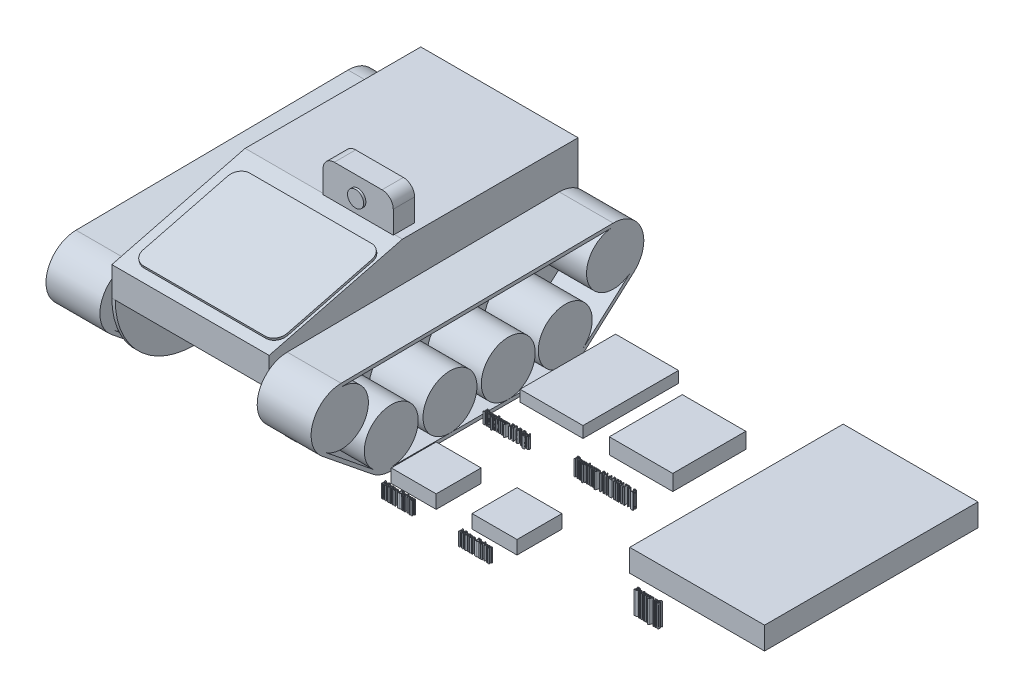
SolidWorks part; units mm, degrees
ref_plane "Спереди" through (0, 0, 0) normal (0, 0, 1) x (1, 0, 0)
ref_plane "Сверху" through (0, 0, 0) normal (0, 1, 0) x (1, 0, 0)
ref_plane "Справа" through (0, 0, 0) normal (1, 0, 0) x (0, 0, -1)
sketch "Эскиз1" plane through (0, 0, 0) normal (1, 0, 0) x (0, 0, -1)
  line L2 (-118.6213, 23.4128) -> (-118.6213, -46.5872)
  line L3 (-118.6213, -46.5872) -> (156.3787, -46.5872)
  line L4 (156.3787, 23.4128) -> (156.3787, -46.5872)
  line L14 (-118.6213, 23.4128) -> (156.3787, 23.4128)
  dimension "D1" = 275
  dimension "D2" = 70
extrude "Бобышка-Вытянуть5" add sketch "Эскиз1" against normal blind 3 contours L14 L2 L3 L4
sketch "Эскиз3" plane through (0, 0, 0) normal (1, 0, 0) x (0, 0, -1)
  line L0 (-118.6213, 49.2471) -> (0, 79.5354)
  line L1 (-118.6213, 23.4128) -> (156.3787, 23.4128)
  line L2 (-118.6213, 23.4128) -> (-118.6213, 49.2471)
  line L3 (-118.6213, 49.2471) -> (156.3787, 49.2471)
  line L4 (156.3787, 23.4128) -> (156.3787, 49.2471)
  line L5 (0, 79.5354) -> (156.3787, 79.5354)
  line L6 (156.3787, 79.5354) -> (156.3787, 49.2471)
  dimension "D1" = 275
extrude "Бобышка-Вытянуть6" add sketch "Эскиз3" against normal blind 70 contours L1 L4 L3 L2 | L6 L5 L0 L3
sketch "Эскиз4" plane through (0, 0, 0) normal (1, 0, 0) x (0, 0, -1)
  line L0 (-102.494, 40.7208) -> (139.6566, 43.1324)
  line L1 (-117.341, -1.9438) -> (-73.0232, -37.7622)
  line L2 (155.8507, 1.205) -> (112.8921, -37.025)
  line L3 (-57.9372, -43.0964) -> (96.937, -43.0964)
  line L4 (-102.5239, 43.7206) -> (139.6267, 46.1323)
  line L5 (157.8451, -1.036) -> (114.8865, -39.266)
  line L6 (-57.9372, -46.0964) -> (96.937, -46.0964)
  line L7 (-119.2268, -4.2771) -> (-74.9089, -40.0954)
  arc A0 (-102.494, 40.7208) -> (-117.341, -1.9438) centre (-102.255, 16.722) ccw
  arc A2 (-73.0232, -37.7622) -> (-57.9372, -43.0964) centre (-57.9372, -19.0964) ccw
  arc A11 (96.937, -43.0964) -> (112.8921, -37.025) centre (96.937, -19.0964) ccw
  arc A12 (155.8507, 1.205) -> (139.6566, 43.1324) centre (139.8956, 19.1336) ccw
  circle A13 centre (-102.255, 16.722) radius 24
  circle A16 centre (96.937, -19.0964) radius 24
  circle A19 centre (139.8956, 19.1336) radius 24
  circle A20 centre (-57.9372, -19.0964) radius 24
  circle A21 centre (-5.6546, -19.0964) radius 24
  circle A22 centre (46.2242, -19.0964) radius 24
  arc A23 (157.8451, -1.036) -> (139.6267, 46.1323) centre (139.8956, 19.1336) ccw
  arc A24 (96.937, -46.0964) -> (114.8865, -39.266) centre (96.937, -19.0964) ccw
  arc A25 (-74.9089, -40.0954) -> (-57.9372, -46.0964) centre (-57.9372, -19.0964) ccw
  arc A26 (-102.5239, 43.7206) -> (-119.2268, -4.2771) centre (-102.255, 16.722) ccw
  line M1 (156.3787, -46.5872) -> (156.3787, 79.5354)
  line M4 (-118.6213, 49.2471) -> (-118.6213, -46.5872)
  dimension "D1" = 3
extrude "Бобышка-Вытянуть7" add sketch "Эскиз4" along normal blind 48 separate body contours A2 A20 | A0 A13 M4 | A0 M4 | A21 | A22 | A11 A16 | A22 A19 M1 | A22 M1 | L7 A25 L6 A24 L5 A22 L2 A11 L3 A2 L1 A0 M1 M4 | L5 A23 A22 M1 | L4 A26 A0 L0 A22 A23 M4 M1 | A26 L7 A0 M4
ref_plane "Плоскость5" through (-70, 0, 0) normal (-1, 0, 0) x (0, 0, 1)
mirror "Зеркальное отражение1" about plane through (-70, 0, 0) normal (-1, 0, 0) of bodies 108 111 112 107
fillet "Скругление1" radius 70 2 edges at (-3, -11.5872, 118.6213) (-1.5, -46.5872, 118.6213)
fillet "Скругление2" radius 70 2 edges at (-3, -11.5872, -156.3787) (-1.5, -46.5872, -156.3787)
fillet "Скругление3" radius 70 2 edges at (-137, -11.5872, -156.3787) (-138.5, -46.5872, -156.3787)
fillet "Скругление4" radius 70 2 edges at (-137, -11.5872, 118.6213) (-138.5, -46.5872, 118.6213)
ref_plane "Плоскость6" through (0, 0, 0) normal (0, 0, -1) x (1, 0, 0)
sketch "Эскиз10" plane through (0, 0, 0) normal (0, 0, -1) x (1, 0, 0)
  line L0 (-70, -79.5354) -> (0, -79.5354) construction
  line L1 (-69.6217, -109.5354) -> (-7.1459, -109.5354)
  line L2 (-69.6217, -109.5354) -> (-69.6217, -79.5354)
  line L3 (-69.6217, -79.5354) -> (-7.1459, -79.5354)
  line L4 (-7.1459, -109.5354) -> (-7.1459, -79.5354)
  dimension "D1" = 30
extrude "Бобышка-Вытянуть14" add sketch "Эскиз10" against normal blind 1 and the other way blind 18
sketch "Эскиз12" plane through (0, -8.4881, 1) normal (0, 0, 1) x (1, 0, 0)
  circle A0 centre (-38.6725, 101.334) radius 7.1777
extrude "Бобышка-Вытянуть15" add sketch "Эскиз12" along normal blind 2
fillet "Скругление5" radius 10 1 edges at (-7.1459, 109.5354, -8.5)
fillet "Скругление6" radius 10 1 edges at (-69.6217, 109.5354, -8.5)
ref_plane "Плоскость7" through (0, 74.6673, 19.0653) normal (0, -0.9689, -0.2474) x (-1, 0, 0)
sketch "Эскиз13" plane through (0, 74.6673, 19.0653) normal (0, 0.9689, 0.2474) x (1, 0, 0)
  line L0 (-130.6595, 4.4916) -> (-130.6595, -93.1708)
  line L1 (-127.6595, 1.4916) -> (-5.27, 1.4916)
  line L2 (-127.6595, 1.4916) -> (-127.6595, -90.1708)
  line L3 (-127.6595, -90.1708) -> (-5.27, -90.1708)
  line L4 (-5.27, 1.4916) -> (-5.27, -90.1708)
  line L9 (-130.6595, -93.1708) -> (-2.27, -93.1708)
  line L10 (-2.27, 4.4916) -> (-2.27, -93.1708)
  line L11 (-130.6595, 4.4916) -> (-2.27, 4.4916)
  line M11 (-70, -102.7501) -> (-70, 19.6769)
  dimension "D1" = 3
extrude "Бобышка-Вытянуть16" add sketch "Эскиз13" along direction (0, -0.9689, -0.2474) on the side of the normal blind 2 contours L4 L1 L3 M11 | L2 L3 L1 M11 | L11 L0 L9 L3 L2 L1 M11 | L11 L1 L4 L3 L9 L10 M11
fillet "Скругление7" radius 10 1 edges at (-2.27, 76.7475, 14.9607)
fillet "Скругление8" radius 10 1 edges at (-2.27, 52.5859, 109.5871)
fillet "Скругление9" radius 10 1 edges at (-130.6595, 52.5859, 109.5871)
fillet "Скругление10" radius 10 1 edges at (-130.6595, 76.7475, 14.9607)
sketch "Эскиз16" plane through (0, 0, 0) normal (0, 0, -1) x (1, 0, 0)
  circle A0 centre (-38.6725, -92.8459) radius 2
  circle A2 centre (-38.6725, -92.8459) radius 4
extrude "Вырез-Вытянуть1" cut sketch "Эскиз16" against normal blind 1
sketch "Эскиз18" plane through (0, 0, 45.2657) normal (0, 1, 0) x (1, 0, 0)
  line L1 (98.5208, 136.4886) -> (154.5208, 136.4886)
  line L2 (98.5208, 136.4886) -> (98.5208, 51.4886)
  line L3 (98.5208, 51.4886) -> (154.5208, 51.4886)
  line L4 (154.5208, 136.4886) -> (154.5208, 51.4886)
  text T0 "Raspberry PI 5 8gb"
  dimension "D1" = 85
  dimension "D2" = 56
extrude "Raspberry_PI5" add sketch "Эскиз18" along normal blind 10 separate body
sketch "Эскиз19" plane through (0, 0, 0) normal (0, 1, 0) x (1, 0, 0)
  line L1 (178.872, 70.2749) -> (235.372, 70.2749)
  line L2 (178.872, 70.2749) -> (178.872, 5.2749)
  line L3 (178.872, 5.2749) -> (235.372, 5.2749)
  line L4 (235.372, 70.2749) -> (235.372, 5.2749)
  text T0 "Raspberry Pi AI HAT+ 2"
  dimension "D1" = 65
  dimension "D2" = 56.5
extrude "Raspberry_Pi_AI_HAT+2" add sketch "Эскиз19" along normal blind 14 separate body contours L2 L1 L4 L3
sketch "Эскиз22" plane through (5.9171, 0, 82.1954) normal (0, 1, 0) x (1, 0, 0)
  line L1 (273.2549, 195.3728) -> (393.2549, 195.3728)
  line L2 (273.2549, 195.3728) -> (273.2549, 5.3728)
  line L3 (273.2549, 5.3728) -> (393.2549, 5.3728)
  line L4 (393.2549, 195.3728) -> (393.2549, 5.3728)
  text T0 "Baterry x6"
  dimension "D1" = 120
  dimension "D2" = 190
extrude "Baterry" add sketch "Эскиз22" along normal blind 20 separate body
sketch "Эскиз23" plane through (0, 0, 0) normal (0, 1, 0) x (1, 0, 0)
  line L0 (174.9896, -72.971) -> (214.9896, -72.971)
  line L1 (103.8359, -73.7659) -> (143.8359, -73.7659)
  line L2 (103.8359, -73.7659) -> (103.8359, -113.7659)
  line L3 (103.8359, -113.7659) -> (143.8359, -113.7659)
  line L4 (143.8359, -73.7659) -> (143.8359, -113.7659)
  line L5 (174.9896, -72.971) -> (174.9896, -112.971)
  line L6 (174.9896, -112.971) -> (214.9896, -112.971)
  line L7 (214.9896, -72.971) -> (214.9896, -112.971)
  text T0 "Motor Driver"
  text T1 "Motor Driver"
  dimension "D1" = 40
  dimension "D2" = 40
  dimension "D3" = 40
  dimension "D4" = 40
extrude "Motor_Driver" add sketch "Эскиз23" along normal blind 12 separate body
